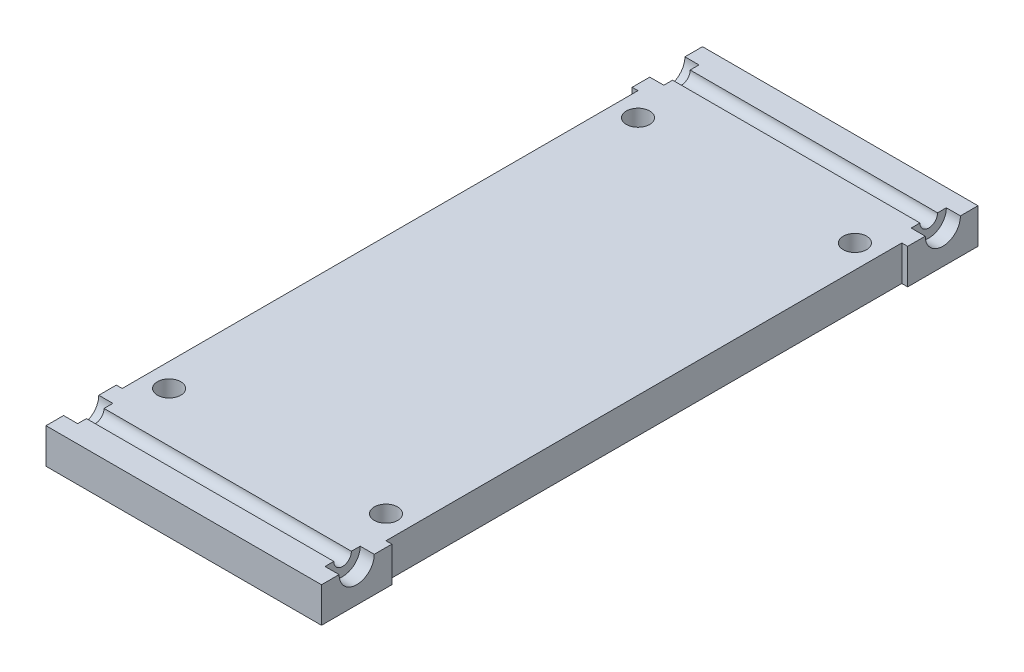
SolidWorks part; units mm, degrees
other "标注1"
sketch "草图3" plane through (-22.25, 4, -10) normal (-0.231, 0.6469, -0.7268) x (-0.9696, -0.2151, 0.1167)
ref_plane "前视基准面" through (0, 0, 0) normal (0, 0, 1) x (1, 0, 0)
ref_plane "上视基准面" through (0, 0, 0) normal (0, 1, 0) x (1, 0, 0)
ref_plane "右视基准面" through (0, 0, 0) normal (1, 0, 0) x (0, 0, -1)
other "Configuration Table"
sketch "草图4" plane through (0, 0, 0) normal (0, 1, 0) x (1, 0, 0)
  line L1 (-11.75, -28) -> (11.75, -28)
  line L2 (-11.75, -28) -> (-11.75, 28)
  line L3 (-11.75, 28) -> (11.75, 28)
  line L4 (11.75, -28) -> (11.75, 28)
  line L5 (-11.75, -28) -> (11.75, 28) construction
  line L6 (-11.75, 28) -> (11.75, -28) construction
  point P0 (0, 0)
  dimension "D1" = 56
  dimension "D2" = 23.5
extrude "凸台-拉伸1" add sketch "草图4" along normal blind 3
sketch "草图5" plane through (11.75, 0, 0) normal (1, 0, 0) x (0, 0, -1)
  line L0 (-28, 3) -> (28, 3) construction
  line L1 (-25, 3) -> (0, 3) construction
  line L2 (0, 3) -> (25, 3) construction
  circle A0 centre (-25, 3) radius 1.5
  circle A2 centre (25, 3) radius 1.5
  circle A3 centre (-25, 3) radius 0.75
  circle A5 centre (25, 3) radius 0.75
  dimension "D1" = 3
  dimension "D3" = 50
  dimension "D4" = 1.5
extrude "切除-拉伸1" cut sketch "草图5" against normal through all contours A3 | A5
extrude "切除-拉伸4" cut sketch "草图5<3>" against normal blind 1.2 contours A2 | A0
sketch "草图5<3>" plane through (11.75, 0, 0) normal (1, 0, 0) x (0, 0, -1) same geometry as "草图5"
extrude "切除-拉伸5" cut sketch "草图5<4>" along normal blind 1.2 from surface contours A0 | A2 starting at face at (-11.75, 2.0625, 0)
sketch "草图5<4>" plane through (11.75, 0, 0) normal (1, 0, 0) x (0, 0, -1) same geometry as "草图5"
sketch "草图6" plane through (0, 0, 0) normal (0, -1, 0) x (1, 0, 0)
  line L0 (-9.25, 0) -> (9.25, 0) construction
  line L1 (-11.75, -28) -> (-11.75, 28) construction
  line L3 (-9.25, 6) -> (-9.25, -6) construction
  line L4 (9.25, 20) -> (9.25, -20) construction
  circle A2 centre (-9.25, -20) radius 1.5
  circle A3 centre (-9.25, -20) radius 1
  circle A4 centre (9.25, -20) radius 1.5
  circle A5 centre (9.25, -20) radius 1
  circle A6 centre (-9.25, 20) radius 1
  circle A7 centre (-9.25, 20) radius 1.5
  circle A8 centre (9.25, 20) radius 1.5
  circle A9 centre (9.25, 20) radius 1
  dimension "D1" = 3
  dimension "D2" = 2
  dimension "D3" = 2.5
  dimension "D4" = 6
  dimension "D5" = 20
extrude "切除-拉伸2" cut sketch "草图6" against normal offset from surface (1 mm away) 2 up to face at (0, 3, 0)
extrude "切除-拉伸3" cut sketch "草图6<2>" against normal through all contours A3 | A6 | A5 | A9
sketch "草图6<2>" plane through (0, 0, 0) normal (0, -1, 0) x (1, 0, 0) same geometry as "草图6"
sketch "草图7" plane through (-11.75, 0, 0) normal (-1, 0, 0) x (0, 0, 1)
  line L0 (-23.5, 3) -> (23.5, 3) construction
  line L1 (-22, 3) -> (22, 3)
  line L2 (-22, 3) -> (-22, 0)
  line L3 (-22, 0) -> (22, 0)
  line L4 (22, 3) -> (22, 0)
  line L5 (-28, 0) -> (28, 0) construction
  line L7 (-28, 3) -> (-22, 3) construction
  line L8 (22, 3) -> (28, 3) construction
  circle A0 centre (-25, 3) radius 0.5 construction
  circle A1 centre (25, 3) radius 0.5 construction
  point P18 (0, 0)
  point P21 (25, 3)
extrude "切除-拉伸8" cut sketch "草图7" against normal blind 0.5
extrude "切除-拉伸9" cut sketch "草图7<2>" along normal blind 0.5 from surface starting at face at (11.75, 1.875, 0)
sketch "草图7<2>" plane through (-11.75, 0, 0) normal (-1, 0, 0) x (0, 0, 1) same geometry as "草图7"
